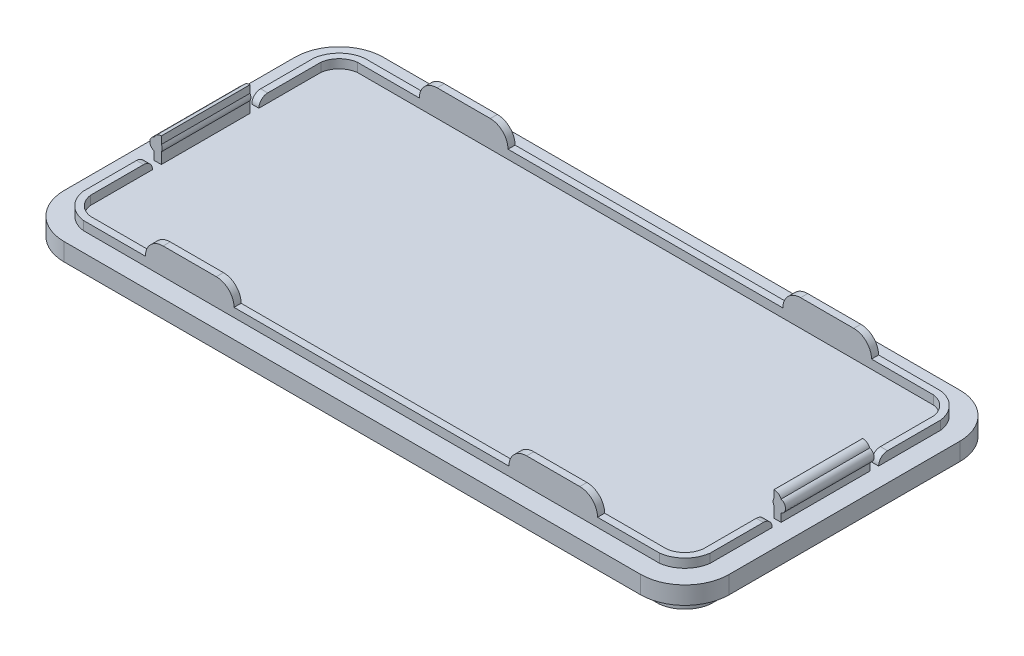
SolidWorks part; units mm, degrees
ref_plane "前视基准面" through (0, 0, 0) normal (0, 0, 1) x (1, 0, 0)
ref_plane "上视基准面" through (0, 0, 0) normal (0, 1, 0) x (1, 0, 0)
ref_plane "右视基准面" through (0, 0, 0) normal (1, 0, 0) x (0, 0, -1)
sketch "zero" plane through (0, 0, 0) normal (0, 1, 0) x (1, 0, 0)
  line L1 (-29.5, 15) -> (29.5, 15)
  line L2 (-32.5, 12) -> (-32.5, -12)
  line L3 (-29.5, -15) -> (29.5, -15)
  line L4 (32.5, 12) -> (32.5, -12)
  line L5 (-32.5, 15) -> (32.5, -15) construction
  line L6 (-32.5, -15) -> (32.5, 15) construction
  line L7 (-25.7, -15) -> (-14.5, -15)
  line L8 (-25.7, -15) -> (-25.7, -9.6569)
  line L9 (-25.7, -9.6569) -> (-14.5, -9.6569)
  line L10 (-14.5, -15) -> (-14.5, -9.6569)
  line L11 (5.2, -15) -> (12.7, -15)
  line L12 (5.2, -15) -> (5.2, -11)
  line L13 (5.2, -11) -> (12.7, -11)
  line L14 (12.7, -15) -> (12.7, -11)
  line L15 (17.8, -15) -> (25.3, -15)
  line L16 (17.8, -15) -> (17.8, -11)
  line L17 (17.8, -11) -> (25.3, -11)
  line L18 (25.3, -15) -> (25.3, -11)
  line L19 (-32.5, 7.7) -> (-19.5, 7.7)
  line L20 (-32.5, 7.7) -> (-32.5, -4.3)
  line L21 (-32.5, -4.3) -> (-19.5, -4.3)
  line L22 (-19.5, 7.7) -> (-19.5, -4.3)
  line L23 (-25.5, 14) -> (25.5, 14)
  line L24 (-25.5, 14) -> (-25.5, 8.8)
  line L25 (-25.5, 8.8) -> (25.5, 8.8)
  line L26 (25.5, 14) -> (25.5, 8.8)
  line L27 (-19.5, 7.2329) -> (-35.5, 7.2329)
  line L28 (-19.5, 7.2329) -> (-19.5, -3.7671)
  line L29 (-19.5, -3.7671) -> (-35.5, -3.7671)
  line L30 (-35.5, 7.2329) -> (-35.5, -3.7671)
  arc A0 (29.5, -15) -> (32.5, -12) centre (29.5, -12) ccw
  arc A1 (29.5, 15) -> (32.5, 12) centre (29.5, 12) cw
  arc A2 (-32.5, -12) -> (-29.5, -15) centre (-29.5, -12) ccw
  arc A3 (-29.5, 15) -> (-32.5, 12) centre (-29.5, 12) ccw
  circle A4 centre (-29, 11.4) radius 3
  circle A5 centre (-29, -11.5) radius 3
  circle A6 centre (29, 11.4) radius 3
  circle A7 centre (29, -11.5) radius 3
  circle A8 centre (-29, 11.4) radius 1.375
  circle A9 centre (-29, -11.5) radius 1.375
  circle A10 centre (29, -11.5) radius 1.375
  circle A11 centre (29, 11.4) radius 1.375
  point P0 (0, 0)
  dimension "D3" = 3
  dimension "D4" = 6
  dimension "D9" = 2.75
  dimension "D1" = 65
  dimension "D2" = 30
  dimension "D5" = 3.6
  dimension "D6" = 3.5
  dimension "D7" = 3.5
  dimension "D8" = 3.5
  dimension "D10" = 12
  dimension "D11" = 7.3
  dimension "D12" = 13
  dimension "D13" = 11.2
  dimension "D14" = 6.8
  dimension "D15" = 19.7
  dimension "D16" = 7.5
  dimension "D17" = 7.5
  dimension "D18" = 5.1
  dimension "D19" = 4
  dimension "D20" = 5.2
  dimension "D21" = 7
  dimension "D22" = 7
  dimension "D23" = 1
  dimension "D24" = 11
  dimension "D25" = 16
sketch "sugar" plane through (0, 0, 0) normal (0, 1, 0) x (1, 0, 0)
  line L1 (-29.5, 15) -> (29.5, 15)
  line L2 (-32.5, 12) -> (-32.5, -12)
  line L3 (-29.5, -15) -> (29.5, -15)
  line L4 (32.5, 12) -> (32.5, -12)
  line L5 (-32.5, 15) -> (32.5, -15) construction
  line L6 (-32.5, -15) -> (32.5, 15) construction
  line L7 (23.5, -11.5) -> (19.5, -11.5)
  line L8 (23.5, -11.5) -> (23.5, -13.9082)
  line L9 (23.5, -13.9082) -> (19.5, -13.9082)
  line L10 (19.5, -11.5) -> (19.5, -13.9082)
  line L11 (16, -11.0071) -> (8.5, -11.0071)
  line L12 (16, -11.0071) -> (16, -15)
  line L13 (16, -15) -> (8.5, -15)
  line L14 (8.5, -11.0071) -> (8.5, -15)
  line L15 (20.5, -13.9082) -> (22.5, -13.9082)
  line L16 (20.5, -13.9082) -> (20.5, -14.8173)
  line L17 (20.5, -14.8173) -> (22.5, -14.8173)
  line L18 (22.5, -13.9082) -> (22.5, -14.8173)
  arc A0 (29.5, 15) -> (32.5, 12) centre (29.5, 12) cw
  arc A1 (29.5, -15) -> (32.5, -12) centre (29.5, -12) ccw
  arc A2 (-32.5, -12) -> (-29.5, -15) centre (-29.5, -12) ccw
  arc A3 (-29.5, 15) -> (-32.5, 12) centre (-29.5, 12) ccw
  circle A4 centre (-29, 11.4) radius 3
  circle A5 centre (-29, 11.4) radius 1.375
  circle A6 centre (-29, -11.5) radius 3
  circle A7 centre (-29, -11.5) radius 1.375
  circle A8 centre (29, 11.4) radius 3
  circle A9 centre (29, 11.4) radius 1.375
  circle A10 centre (29, -11.5) radius 3
  circle A11 centre (29, -11.5) radius 1.375
  dimension "D3" = 3
  dimension "D1" = 65
  dimension "D2" = 30
  dimension "D4" = 9
  dimension "D5" = 4
  dimension "D6" = 3.5
  dimension "D7" = 7.5
  dimension "D8" = 2
  dimension "D9" = 1
sketch "case" plane through (0, 0, 0) normal (0, 1, 0) x (1, 0, 0)
  line L1 (-34.0422, 18) -> (30.9578, 18)
  line L2 (-39.0422, 13) -> (-39.0422, -13)
  line L3 (-34.0422, -18) -> (30.9578, -18)
  line L4 (35.9578, 13) -> (35.9578, -13)
  line L5 (-39.0422, 18) -> (35.9578, -18) construction
  line L6 (-39.0422, -18) -> (35.9578, 18) construction
  arc A0 (-39.0422, -13) -> (-34.0422, -18) centre (-34.0422, -13) ccw
  arc A1 (30.9578, -18) -> (35.9578, -13) centre (30.9578, -13) ccw
  arc A2 (30.9578, 18) -> (35.9578, 13) centre (30.9578, 13) cw
  arc A3 (-34.0422, 18) -> (-39.0422, 13) centre (-34.0422, 13) ccw
  point P0 (-1.5422, 0)
  point P3 (-1.5422, 0)
  dimension "D3" = 5
  dimension "D1" = 75
  dimension "D2" = 36
extrude "凸台-拉伸2" add sketch "case" along normal blind 2
sketch "草图2" plane through (0, 0, 0) normal (0, 1, 0) x (1, 0, 0)
  line L0 (-39.0422, 13) -> (-39.0422, -13) construction
  line L1 (30.9578, 18) -> (-34.0422, 18) construction
  line L4 (-34.0422, -15.05) -> (30.9578, -15.05)
  line L5 (33.0078, -13) -> (33.0078, 13)
  line L6 (30.9578, 15.05) -> (-34.0422, 15.05)
  line L7 (-36.0922, 13) -> (-36.0922, -13)
  line L12 (33.8078, -13) -> (33.8078, 13)
  line L13 (30.9578, 15.85) -> (-34.0422, 15.85)
  line L14 (-36.8922, 13) -> (-36.8922, -13)
  line L15 (-34.0422, -15.85) -> (30.9578, -15.85)
  arc A4 (30.9578, -15.05) -> (33.0078, -13) centre (30.6303, -12.6725) ccw
  arc A5 (33.0078, 13) -> (30.9578, 15.05) centre (30.6303, 12.6725) ccw
  arc A6 (-34.0422, 15.05) -> (-36.0922, 13) centre (-33.7147, 12.6725) ccw
  arc A7 (-36.0922, -13) -> (-34.0422, -15.05) centre (-33.7147, -12.6725) ccw
  arc A12 (30.9578, -15.85) -> (33.8078, -13) centre (30.535, -12.5772) ccw
  arc A13 (33.8078, 13) -> (30.9578, 15.85) centre (30.535, 12.5772) ccw
  arc A14 (-34.0422, 15.85) -> (-36.8922, 13) centre (-33.6194, 12.5772) ccw
  arc A15 (-36.8922, -13) -> (-34.0422, -15.85) centre (-33.6194, -12.5772) ccw
ref_plane "基准面1" through (0, 2, 0) normal (0, 1, 0) x (1, 0, 0)
sketch "草图3" plane through (0, 2, 0) normal (0, 1, 0) x (1, 0, 0)
  line L4 (-34.0422, -15.05) -> (30.9578, -15.05)
  line L5 (33.0078, -13) -> (33.0078, 13)
  line L6 (30.9578, 15.05) -> (-34.0422, 15.05)
  line L7 (-36.0922, 13) -> (-36.0922, -13)
  line L8 (-34.0422, -15.05) -> (30.9578, -15.05)
  line L9 (33.0078, -13) -> (33.0078, 13)
  line L10 (30.9578, 15.05) -> (-34.0422, 15.05)
  line L11 (-36.0922, 13) -> (-36.0922, -13)
  line L12 (-36.8922, 13) -> (-36.8922, -13)
  line L13 (-34.0422, -15.85) -> (30.9578, -15.85)
  line L14 (33.8078, -13) -> (33.8078, 13)
  line L15 (30.9578, 15.85) -> (-34.0422, 15.85)
  line L16 (-36.8922, 13) -> (-36.8922, -13)
  line L17 (-34.0422, -15.85) -> (30.9578, -15.85)
  line L18 (33.8078, -13) -> (33.8078, 13)
  line L19 (30.9578, 15.85) -> (-34.0422, 15.85)
  arc A4 (30.9578, -15.05) -> (33.0078, -13) centre (30.6303, -12.6725) ccw
  arc A5 (33.0078, 13) -> (30.9578, 15.05) centre (30.6303, 12.6725) ccw
  arc A6 (-34.0422, 15.05) -> (-36.0922, 13) centre (-33.7147, 12.6725) ccw
  arc A7 (-36.0922, -13) -> (-34.0422, -15.05) centre (-33.7147, -12.6725) ccw
  arc A8 (30.9578, -15.05) -> (33.0078, -13) centre (30.6303, -12.6725) ccw
  arc A9 (33.0078, 13) -> (30.9578, 15.05) centre (30.6303, 12.6725) ccw
  arc A10 (-34.0422, 15.05) -> (-36.0922, 13) centre (-33.7147, 12.6725) ccw
  arc A11 (-36.0922, -13) -> (-34.0422, -15.05) centre (-33.7147, -12.6725) ccw
  arc A12 (-36.8922, -13) -> (-34.0422, -15.85) centre (-33.6194, -12.5772) ccw
  arc A13 (30.9578, -15.85) -> (33.8078, -13) centre (30.535, -12.5772) ccw
  arc A14 (33.8078, 13) -> (30.9578, 15.85) centre (30.535, 12.5772) ccw
  arc A15 (-34.0422, 15.85) -> (-36.8922, 13) centre (-33.6194, 12.5772) ccw
  arc A16 (-36.8922, -13) -> (-34.0422, -15.85) centre (-33.6194, -12.5772) ccw
  arc A17 (30.9578, -15.85) -> (33.8078, -13) centre (30.535, -12.5772) ccw
  arc A18 (33.8078, 13) -> (30.9578, 15.85) centre (30.535, 12.5772) ccw
  arc A19 (-34.0422, 15.85) -> (-36.8922, 13) centre (-33.6194, 12.5772) ccw
  dimension "D1" = 0
  dimension "D2" = 0
extrude "凸台-拉伸4" add sketch "草图3" along normal blind 1
ref_plane "基准面3" through (33.8078, 0, 0) normal (1, 0, 0) x (0, 0, -1)
sketch "草图7" plane through (0, 2, 0) normal (0, 1, 0) x (1, 0, 0)
  line L0 (-36.8922, 13) -> (-36.8922, -13) construction
  line L1 (-36.8922, 5) -> (-36.0922, 5)
  line L2 (-36.8922, 5) -> (-36.8922, -5)
  line L3 (-36.8922, -5) -> (-36.0922, -5)
  line L4 (-36.0922, 5) -> (-36.0922, -5)
  line L5 (-36.0922, 13) -> (-36.0922, -13) construction
  point P10 (-36.0922, 0)
  dimension "D1" = 5
  dimension "D2" = 10
extrude "凸台-拉伸8" add sketch "草图7" along normal blind 2.8
ref_plane "基准面5" through (0, 0, 5) normal (0, 0, 1) x (1, 0, 0)
sketch "草图8" plane through (0, 0, 5) normal (0, 0, 1) x (1, 0, 0)
  line L0 (-34.0422, 2) -> (-39.0422, 2) construction
  line L1 (-36.8922, 4.8) -> (-36.8922, 3) construction
  circle A0 centre (-36.6922, 3.6) radius 0.7
  dimension "D1" = 1.4
  dimension "D2" = 1.6
  dimension "D3" = 0.2
extrude "凸台-拉伸9" add sketch "草图8" against normal blind 10
fillet "圆角1" radius 0.85 1 edges at (-36.8922, 4.8, 0)
ref_plane "基准面7" through (-36.8922, 0, 0) normal (-1, 0, 0) x (0, 0, 1)
sketch "草图11" plane through (-36.8922, 0, 0) normal (-1, 0, 0) x (0, 0, 1)
  line L0 (-13, 2) -> (13, 2) construction
  line L1 (5, 3) -> (6, 3)
  line L2 (5, 3) -> (5, 2)
  line L3 (5, 2) -> (6, 2)
  line L4 (6, 3) -> (6, 2)
  line L6 (-5, 3) -> (-6, 3)
  line L7 (-5, 3) -> (-5, 2)
  line L8 (-5, 2) -> (-6, 2)
  line L9 (-6, 3) -> (-6, 2)
  dimension "D1" = 1
  dimension "D2" = 1
extrude "切除-拉伸1" cut sketch "草图11" against normal blind 1.2
fillet "圆角2" radius 1 2 edges at (-36.4922, 3, 6) (-36.4922, 3, -6)
ref_plane "基准面8" through (0, 0, 0) normal (0, -1, 0) x (-1, 0, 0)
sketch "草图13" plane through (0, 3, 0) normal (0, 1, 0) x (1, 0, 0)
  line L0 (33.0078, -13) -> (33.0078, 13) construction
  line L1 (33.0078, 5) -> (33.8078, 5)
  line L2 (33.0078, 5) -> (33.0078, -5)
  line L3 (33.0078, -5) -> (33.8078, -5)
  line L4 (33.8078, 5) -> (33.8078, -5)
  line L5 (33.8078, -13) -> (33.8078, 13) construction
  line L7 (35.9578, -13) -> (35.9578, 13) construction
  point P12 (35.9578, 0)
  point P13 (33.8078, 0)
  dimension "D1" = 10
extrude "凸台-拉伸10" add sketch "草图13" along normal blind 1.8
sketch "草图14" plane through (0, 0, 5) normal (0, 0, 1) x (1, 0, 0)
  line L0 (33.8078, 2) -> (30.9578, 2) construction
  line L1 (33.8078, 4.8) -> (33.8078, 3) construction
  circle A0 centre (33.6078, 3.6) radius 0.7
  dimension "D2" = 1.4
  dimension "D1" = 1.6
  dimension "D3" = 0.2
extrude "凸台-拉伸11" add sketch "草图14" against normal blind 10
fillet "圆角3" radius 0.85 1 edges at (33.8078, 4.8, 0)
sketch "草图15" plane through (0, 3, 0) normal (0, 1, 0) x (1, 0, 0)
  line L0 (33.8078, 5) -> (33.8078, 13) construction
  line L1 (33.0078, 5) -> (33.8078, 5)
  line L2 (33.0078, 5) -> (33.0078, 6)
  line L3 (33.0078, 6) -> (33.8078, 6)
  line L4 (33.8078, 5) -> (33.8078, 6)
  line L5 (33.8078, -13) -> (33.8078, -5) construction
  line L6 (33.0078, -5) -> (33.8078, -5)
  line L7 (33.0078, -5) -> (33.0078, -6)
  line L8 (33.0078, -6) -> (33.8078, -6)
  line L9 (33.8078, -5) -> (33.8078, -6)
  dimension "D1" = 1
  dimension "D2" = 1
extrude "切除-拉伸3" cut sketch "草图15" against normal blind 1
fillet "圆角4" radius 1 2 edges at (33.4078, 3, 6) (33.4078, 3, -6)
sketch "草图16" plane through (0, 2, 0) normal (0, 1, 0) x (1, 0, 0)
  line L4 (-34.0422, -15.05) -> (30.9578, -15.05)
  line L5 (33.0078, -13) -> (33.0078, 13)
  line L6 (30.9578, 15.05) -> (-34.0422, 15.05)
  line L7 (-36.0922, 13) -> (-36.0922, -13)
  line L8 (-34.0422, -15.05) -> (30.9578, -15.05)
  line L9 (33.0078, -13) -> (33.0078, 13)
  line L10 (30.9578, 15.05) -> (-34.0422, 15.05)
  line L11 (-36.0922, 13) -> (-36.0922, -13)
  arc A4 (30.9578, -15.05) -> (33.0078, -13) centre (30.6303, -12.6725) ccw
  arc A5 (33.0078, 13) -> (30.9578, 15.05) centre (30.6303, 12.6725) ccw
  arc A6 (-34.0422, 15.05) -> (-36.0922, 13) centre (-33.7147, 12.6725) ccw
  arc A7 (-36.0922, -13) -> (-34.0422, -15.05) centre (-33.7147, -12.6725) ccw
  arc A8 (30.9578, -15.05) -> (33.0078, -13) centre (30.6303, -12.6725) ccw
  arc A9 (33.0078, 13) -> (30.9578, 15.05) centre (30.6303, 12.6725) ccw
  arc A10 (-34.0422, 15.05) -> (-36.0922, 13) centre (-33.7147, 12.6725) ccw
  arc A11 (-36.0922, -13) -> (-34.0422, -15.05) centre (-33.7147, -12.6725) ccw
  dimension "D1" = 0
extrude "凸台-拉伸12" add sketch "草图2" against normal blind 2
sketch "草图18" plane through (0, 0, 0) normal (0, -1, 0) x (1, 0, 0)
  line L2 (-34.0422, 18) -> (30.9578, 18) construction
  line L3 (-39.0422, -13) -> (-39.0422, 13) construction
  circle A0 centre (-37.3172, 15.9) radius 3.225
  circle A1 centre (-37.3172, 15.9) radius 2.225
  circle A2 centre (-29.3672, 15.9) radius 2.225
  circle A3 centre (-29.3672, 15.9) radius 3.225
  circle A4 centre (-21.4172, 15.9) radius 2.225
  circle A5 centre (-21.4172, 15.9) radius 3.225
  circle A6 centre (-13.4672, 15.9) radius 2.225
  circle A7 centre (-13.4672, 15.9) radius 3.225
  circle A8 centre (-5.5172, 15.9) radius 2.225
  circle A9 centre (-5.5172, 15.9) radius 3.225
  circle A10 centre (2.4328, 15.9) radius 2.225
  circle A11 centre (2.4328, 15.9) radius 3.225
  circle A12 centre (10.3828, 15.9) radius 2.225
  circle A13 centre (10.3828, 15.9) radius 3.225
  circle A14 centre (18.3328, 15.9) radius 2.225
  circle A15 centre (18.3328, 15.9) radius 3.225
  circle A16 centre (26.2828, 15.9) radius 2.225
  circle A17 centre (26.2828, 15.9) radius 3.225
  circle A18 centre (34.2328, 15.9) radius 2.225
  circle A19 centre (34.2328, 15.9) radius 3.225
  circle A20 centre (-29.3672, 7.95) radius 2.225
  circle A21 centre (-29.3672, 7.95) radius 3.225
  circle A22 centre (-21.4172, 7.95) radius 2.225
  circle A23 centre (-21.4172, 7.95) radius 3.225
  circle A24 centre (-13.4672, 7.95) radius 2.225
  circle A25 centre (-13.4672, 7.95) radius 3.225
  circle A26 centre (-5.5172, 7.95) radius 2.225
  circle A27 centre (-5.5172, 7.95) radius 3.225
  circle A28 centre (2.4328, 7.95) radius 2.225
  circle A29 centre (2.4328, 7.95) radius 3.225
  circle A30 centre (10.3828, 7.95) radius 2.225
  circle A31 centre (10.3828, 7.95) radius 3.225
  circle A32 centre (18.3328, 7.95) radius 2.225
  circle A33 centre (18.3328, 7.95) radius 3.225
  circle A34 centre (26.2828, 7.95) radius 2.225
  circle A35 centre (26.2828, 7.95) radius 3.225
  circle A36 centre (34.2328, 7.95) radius 2.225
  circle A37 centre (34.2328, 7.95) radius 3.225
  circle A38 centre (-29.3672, 0) radius 2.225
  circle A39 centre (-29.3672, 0) radius 3.225
  circle A40 centre (-21.4172, 0) radius 2.225
  circle A41 centre (-21.4172, 0) radius 3.225
  circle A42 centre (-13.4672, 0) radius 2.225
  circle A43 centre (-13.4672, 0) radius 3.225
  circle A44 centre (-5.5172, 0) radius 2.225
  circle A45 centre (-5.5172, 0) radius 3.225
  circle A46 centre (2.4328, 0) radius 2.225
  circle A47 centre (2.4328, 0) radius 3.225
  circle A48 centre (10.3828, 0) radius 2.225
  circle A49 centre (10.3828, 0) radius 3.225
  circle A50 centre (18.3328, 0) radius 2.225
  circle A51 centre (18.3328, 0) radius 3.225
  circle A52 centre (26.2828, 0) radius 2.225
  circle A53 centre (26.2828, 0) radius 3.225
  circle A54 centre (34.2328, 0) radius 2.225
  circle A55 centre (34.2328, 0) radius 3.225
  circle A56 centre (-29.3672, -7.95) radius 2.225
  circle A57 centre (-29.3672, -7.95) radius 3.225
  circle A58 centre (-21.4172, -7.95) radius 2.225
  circle A59 centre (-21.4172, -7.95) radius 3.225
  circle A60 centre (-13.4672, -7.95) radius 2.225
  circle A61 centre (-13.4672, -7.95) radius 3.225
  circle A62 centre (-5.5172, -7.95) radius 2.225
  circle A63 centre (-5.5172, -7.95) radius 3.225
  circle A64 centre (2.4328, -7.95) radius 2.225
  circle A65 centre (2.4328, -7.95) radius 3.225
  circle A66 centre (10.3828, -7.95) radius 2.225
  circle A67 centre (10.3828, -7.95) radius 3.225
  circle A68 centre (18.3328, -7.95) radius 2.225
  circle A69 centre (18.3328, -7.95) radius 3.225
  circle A70 centre (26.2828, -7.95) radius 2.225
  circle A71 centre (26.2828, -7.95) radius 3.225
  circle A72 centre (34.2328, -7.95) radius 2.225
  circle A73 centre (34.2328, -7.95) radius 3.225
  circle A74 centre (-29.3672, -15.9) radius 2.225
  circle A75 centre (-29.3672, -15.9) radius 3.225
  circle A76 centre (-21.4172, -15.9) radius 2.225
  circle A77 centre (-21.4172, -15.9) radius 3.225
  circle A78 centre (-13.4672, -15.9) radius 2.225
  circle A79 centre (-13.4672, -15.9) radius 3.225
  circle A80 centre (-5.5172, -15.9) radius 2.225
  circle A81 centre (-5.5172, -15.9) radius 3.225
  circle A82 centre (2.4328, -15.9) radius 2.225
  circle A83 centre (2.4328, -15.9) radius 3.225
  circle A84 centre (10.3828, -15.9) radius 2.225
  circle A85 centre (10.3828, -15.9) radius 3.225
  circle A86 centre (18.3328, -15.9) radius 2.225
  circle A87 centre (18.3328, -15.9) radius 3.225
  circle A88 centre (26.2828, -15.9) radius 2.225
  circle A89 centre (26.2828, -15.9) radius 3.225
  circle A90 centre (34.2328, -15.9) radius 2.225
  circle A91 centre (34.2328, -15.9) radius 3.225
  circle A92 centre (-37.3172, 7.95) radius 2.225
  circle A93 centre (-37.3172, 7.95) radius 3.225
  circle A94 centre (-37.3172, 0) radius 2.225
  circle A95 centre (-37.3172, 0) radius 3.225
  circle A96 centre (-37.3172, -7.95) radius 2.225
  circle A97 centre (-37.3172, -7.95) radius 3.225
  circle A98 centre (-37.3172, -15.9) radius 2.225
  circle A99 centre (-37.3172, -15.9) radius 3.225
  dimension "D1" = 6.45
  dimension "D2" = 4.45
  dimension "D3" = 2.1
  dimension "D4" = 1.725
  dimension "D5" = 10
  dimension "D6" = 5
extrude "凸台-拉伸13" add sketch "草图18" along normal blind 2
sketch "草图20" plane through (0, 0, 0) normal (0, -1, 0) x (1, 0, 0)
  line L4 (30.9578, 15.85) -> (29.5074, 15.85)
  line L5 (-36.8922, -11.1469) -> (-36.8922, -12.7031)
  line L6 (-34.0422, -15.85) -> (-32.5918, -15.85)
  line L7 (-36.8922, -11.1469) -> (-36.8922, -12.7031)
  line L8 (30.9578, 15.85) -> (29.5074, 15.85)
  line L10 (-34.0422, -15.85) -> (-32.5918, -15.85)
  line L12 (-36.0922, 13) -> (-36.0922, -13)
  line L13 (-34.0422, -15.05) -> (30.9578, -15.05)
  line L14 (33.0078, -13) -> (33.0078, 13)
  line L15 (30.9578, 15.05) -> (-34.0422, 15.05)
  line L16 (-36.0922, 13) -> (-36.0922, -13)
  line L17 (-34.0422, -15.05) -> (30.9578, -15.05)
  line L18 (33.0078, -13) -> (33.0078, 13)
  line L19 (30.9578, 15.05) -> (-34.0422, 15.05)
  line L34 (-26.1426, -15.85) -> (-24.6418, -15.85)
  line L35 (-26.1426, -15.85) -> (-24.6418, -15.85)
  line L36 (-18.1926, -15.85) -> (-16.6918, -15.85)
  line L37 (-18.1926, -15.85) -> (-16.6918, -15.85)
  line L38 (-10.2426, -15.85) -> (-8.7418, -15.85)
  line L39 (-10.2426, -15.85) -> (-8.7418, -15.85)
  line L40 (-2.2926, -15.85) -> (-0.7918, -15.85)
  line L41 (-2.2926, -15.85) -> (-0.7918, -15.85)
  line L42 (5.6574, -15.85) -> (7.1582, -15.85)
  line L43 (5.6574, -15.85) -> (7.1582, -15.85)
  line L44 (13.6074, -15.85) -> (15.1082, -15.85)
  line L45 (13.6074, -15.85) -> (15.1082, -15.85)
  line L46 (21.5574, -15.85) -> (23.0582, -15.85)
  line L47 (21.5574, -15.85) -> (23.0582, -15.85)
  line L48 (29.5074, -15.85) -> (30.9578, -15.85)
  line L49 (29.5074, -15.85) -> (30.9578, -15.85)
  line L50 (33.8078, -12.7031) -> (33.8078, -11.1469)
  line L51 (33.8078, -12.7031) -> (33.8078, -11.1469)
  line L52 (33.8078, -4.7531) -> (33.8078, -3.1969)
  line L53 (33.8078, -4.7531) -> (33.8078, -3.1969)
  line L54 (33.8078, 3.1969) -> (33.8078, 4.7531)
  line L55 (33.8078, 3.1969) -> (33.8078, 4.7531)
  line L56 (33.8078, 11.1469) -> (33.8078, 12.7031)
  line L57 (33.8078, 11.1469) -> (33.8078, 12.7031)
  line L58 (23.0582, 15.85) -> (21.5574, 15.85)
  line L59 (23.0582, 15.85) -> (21.5574, 15.85)
  line L60 (15.1082, 15.85) -> (13.6074, 15.85)
  line L61 (15.1082, 15.85) -> (13.6074, 15.85)
  line L62 (7.1582, 15.85) -> (5.6574, 15.85)
  line L63 (7.1582, 15.85) -> (5.6574, 15.85)
  line L64 (-0.7918, 15.85) -> (-2.2926, 15.85)
  line L65 (-0.7918, 15.85) -> (-2.2926, 15.85)
  line L66 (-8.7418, 15.85) -> (-10.2426, 15.85)
  line L67 (-8.7418, 15.85) -> (-10.2426, 15.85)
  line L68 (-16.6918, 15.85) -> (-18.1926, 15.85)
  line L69 (-16.6918, 15.85) -> (-18.1926, 15.85)
  line L70 (-24.6418, 15.85) -> (-26.1426, 15.85)
  line L71 (-24.6418, 15.85) -> (-26.1426, 15.85)
  line L72 (-32.5918, 15.85) -> (-34.0422, 15.85)
  line L73 (-32.5918, 15.85) -> (-34.0422, 15.85)
  line L74 (-36.8922, 12.7031) -> (-36.8922, 11.1469)
  line L75 (-36.8922, 12.7031) -> (-36.8922, 11.1469)
  line L76 (-36.8922, 4.7531) -> (-36.8922, 3.1969)
  line L77 (-36.8922, 4.7531) -> (-36.8922, 3.1969)
  line L78 (-36.8922, -3.1969) -> (-36.8922, -4.7531)
  line L79 (-36.8922, -3.1969) -> (-36.8922, -4.7531)
  arc A4 (31.0083, 15.8431) -> (30.9578, 15.85) centre (30.535, 12.5772) ccw
  arc A5 (-34.0422, 15.85) -> (-34.0927, 15.8431) centre (-33.6194, 12.5772) ccw
  arc A6 (-34.0927, -15.8431) -> (-34.0422, -15.85) centre (-33.6194, -12.5772) ccw
  arc A7 (30.9578, -15.85) -> (31.0083, -15.8431) centre (30.535, -12.5772) ccw
  arc A8 (31.0083, 15.8431) -> (30.9578, 15.85) centre (30.535, 12.5772) ccw
  arc A9 (-34.0422, 15.85) -> (-34.0927, 15.8431) centre (-33.6194, 12.5772) ccw
  arc A10 (-34.0927, -15.8431) -> (-34.0422, -15.85) centre (-33.6194, -12.5772) ccw
  arc A11 (30.9578, -15.85) -> (31.0083, -15.8431) centre (30.535, -12.5772) ccw
  arc A12 (-36.0922, -13) -> (-34.0422, -15.05) centre (-33.7147, -12.6725) ccw
  arc A13 (30.9578, -15.05) -> (33.0078, -13) centre (30.6303, -12.6725) ccw
  arc A14 (33.0078, 13) -> (30.9578, 15.05) centre (30.6303, 12.6725) ccw
  arc A15 (-34.0422, 15.05) -> (-36.0922, 13) centre (-33.7147, 12.6725) ccw
  arc A16 (-36.0922, -13) -> (-34.0422, -15.05) centre (-33.7147, -12.6725) ccw
  arc A17 (30.9578, -15.05) -> (33.0078, -13) centre (30.6303, -12.6725) ccw
  arc A18 (33.0078, 13) -> (30.9578, 15.05) centre (30.6303, 12.6725) ccw
  arc A19 (-34.0422, 15.05) -> (-36.0922, 13) centre (-33.7147, 12.6725) ccw
  arc A38 (-36.8922, -12.7031) -> (-34.0927, -15.8431) centre (-37.3172, -15.9) ccw
  arc A39 (-36.8922, -12.7031) -> (-34.0927, -15.8431) centre (-37.3172, -15.9) ccw
  arc A40 (-32.5918, -15.85) -> (-26.1426, -15.85) centre (-29.3672, -15.9) ccw
  arc A41 (-32.5918, -15.85) -> (-26.1426, -15.85) centre (-29.3672, -15.9) ccw
  arc A42 (-24.6418, -15.85) -> (-18.1926, -15.85) centre (-21.4172, -15.9) ccw
  arc A43 (-24.6418, -15.85) -> (-18.1926, -15.85) centre (-21.4172, -15.9) ccw
  arc A44 (-16.6918, -15.85) -> (-10.2426, -15.85) centre (-13.4672, -15.9) ccw
  arc A45 (-16.6918, -15.85) -> (-10.2426, -15.85) centre (-13.4672, -15.9) ccw
  arc A46 (-8.7418, -15.85) -> (-2.2926, -15.85) centre (-5.5172, -15.9) ccw
  arc A47 (-8.7418, -15.85) -> (-2.2926, -15.85) centre (-5.5172, -15.9) ccw
  arc A48 (-0.7918, -15.85) -> (5.6574, -15.85) centre (2.4328, -15.9) ccw
  arc A49 (-0.7918, -15.85) -> (5.6574, -15.85) centre (2.4328, -15.9) ccw
  arc A50 (7.1582, -15.85) -> (13.6074, -15.85) centre (10.3828, -15.9) ccw
  arc A51 (7.1582, -15.85) -> (13.6074, -15.85) centre (10.3828, -15.9) ccw
  arc A52 (15.1082, -15.85) -> (21.5574, -15.85) centre (18.3328, -15.9) ccw
  arc A53 (15.1082, -15.85) -> (21.5574, -15.85) centre (18.3328, -15.9) ccw
  arc A54 (23.0582, -15.85) -> (29.5074, -15.85) centre (26.2828, -15.9) ccw
  arc A55 (23.0582, -15.85) -> (29.5074, -15.85) centre (26.2828, -15.9) ccw
  arc A56 (31.0083, -15.8431) -> (33.8078, -12.7031) centre (34.2328, -15.9) ccw
  arc A57 (31.0083, -15.8431) -> (33.8078, -12.7031) centre (34.2328, -15.9) ccw
  arc A58 (33.8078, -11.1469) -> (33.8078, -4.7531) centre (34.2328, -7.95) ccw
  arc A59 (33.8078, -11.1469) -> (33.8078, -4.7531) centre (34.2328, -7.95) ccw
  arc A60 (33.8078, -3.1969) -> (33.8078, 3.1969) centre (34.2328, 0) ccw
  arc A61 (33.8078, -3.1969) -> (33.8078, 3.1969) centre (34.2328, 0) ccw
  arc A62 (33.8078, 4.7531) -> (33.8078, 11.1469) centre (34.2328, 7.95) ccw
  arc A63 (33.8078, 4.7531) -> (33.8078, 11.1469) centre (34.2328, 7.95) ccw
  arc A64 (33.8078, 12.7031) -> (31.0083, 15.8431) centre (34.2328, 15.9) ccw
  arc A65 (33.8078, 12.7031) -> (31.0083, 15.8431) centre (34.2328, 15.9) ccw
  arc A66 (29.5074, 15.85) -> (23.0582, 15.85) centre (26.2828, 15.9) ccw
  arc A67 (29.5074, 15.85) -> (23.0582, 15.85) centre (26.2828, 15.9) ccw
  arc A68 (21.5574, 15.85) -> (15.1082, 15.85) centre (18.3328, 15.9) ccw
  arc A69 (21.5574, 15.85) -> (15.1082, 15.85) centre (18.3328, 15.9) ccw
  arc A70 (13.6074, 15.85) -> (7.1582, 15.85) centre (10.3828, 15.9) ccw
  arc A71 (13.6074, 15.85) -> (7.1582, 15.85) centre (10.3828, 15.9) ccw
  arc A72 (5.6574, 15.85) -> (-0.7918, 15.85) centre (2.4328, 15.9) ccw
  arc A73 (5.6574, 15.85) -> (-0.7918, 15.85) centre (2.4328, 15.9) ccw
  arc A74 (-2.2926, 15.85) -> (-8.7418, 15.85) centre (-5.5172, 15.9) ccw
  arc A75 (-2.2926, 15.85) -> (-8.7418, 15.85) centre (-5.5172, 15.9) ccw
  arc A76 (-10.2426, 15.85) -> (-16.6918, 15.85) centre (-13.4672, 15.9) ccw
  arc A77 (-10.2426, 15.85) -> (-16.6918, 15.85) centre (-13.4672, 15.9) ccw
  arc A78 (-18.1926, 15.85) -> (-24.6418, 15.85) centre (-21.4172, 15.9) ccw
  arc A79 (-18.1926, 15.85) -> (-24.6418, 15.85) centre (-21.4172, 15.9) ccw
  arc A80 (-26.1426, 15.85) -> (-32.5918, 15.85) centre (-29.3672, 15.9) ccw
  arc A81 (-26.1426, 15.85) -> (-32.5918, 15.85) centre (-29.3672, 15.9) ccw
  arc A82 (-34.0927, 15.8431) -> (-36.8922, 12.7031) centre (-37.3172, 15.9) ccw
  arc A83 (-34.0927, 15.8431) -> (-36.8922, 12.7031) centre (-37.3172, 15.9) ccw
  arc A84 (-36.8922, 11.1469) -> (-36.8922, 4.7531) centre (-37.3172, 7.95) ccw
  arc A85 (-36.8922, 11.1469) -> (-36.8922, 4.7531) centre (-37.3172, 7.95) ccw
  arc A86 (-36.8922, 3.1969) -> (-36.8922, -3.1969) centre (-37.3172, 0) ccw
  arc A87 (-36.8922, 3.1969) -> (-36.8922, -3.1969) centre (-37.3172, 0) ccw
  arc A88 (-36.8922, -4.7531) -> (-36.8922, -11.1469) centre (-37.3172, -7.95) ccw
  arc A89 (-36.8922, -4.7531) -> (-36.8922, -11.1469) centre (-37.3172, -7.95) ccw
  dimension "D1" = 0
  dimension "D2" = 0
extrude "切除-拉伸4" cut sketch "草图20" along normal blind 2
sketch "草图21" plane through (0, 0, 0) normal (0, -1, 0) x (1, 0, 0)
  line L4 (30.9578, 15.05) -> (-34.0422, 15.05)
  line L5 (33.0078, -13) -> (33.0078, 13)
  line L6 (-34.0422, -15.05) -> (30.9578, -15.05)
  line L7 (-36.0922, 13) -> (-36.0922, -13)
  line L8 (30.9578, 15.05) -> (-34.0422, 15.05)
  line L9 (33.0078, -13) -> (33.0078, 13)
  line L10 (-34.0422, -15.05) -> (30.9578, -15.05)
  line L11 (-36.0922, 13) -> (-36.0922, -13)
  line L12 (-36.8922, 13) -> (-36.8922, -13)
  line L13 (30.9578, 15.85) -> (-34.0422, 15.85)
  line L14 (33.8078, -13) -> (33.8078, 13)
  line L15 (-34.0422, -15.85) -> (30.9578, -15.85)
  line L16 (-36.8922, 13) -> (-36.8922, -13)
  line L17 (30.9578, 15.85) -> (-34.0422, 15.85)
  line L18 (33.8078, -13) -> (33.8078, 13)
  line L19 (-34.0422, -15.85) -> (30.9578, -15.85)
  arc A4 (33.0078, 13) -> (30.9578, 15.05) centre (30.6303, 12.6725) ccw
  arc A5 (30.9578, -15.05) -> (33.0078, -13) centre (30.6303, -12.6725) ccw
  arc A6 (-36.0922, -13) -> (-34.0422, -15.05) centre (-33.7147, -12.6725) ccw
  arc A7 (-34.0422, 15.05) -> (-36.0922, 13) centre (-33.7147, 12.6725) ccw
  arc A8 (33.0078, 13) -> (30.9578, 15.05) centre (30.6303, 12.6725) ccw
  arc A9 (30.9578, -15.05) -> (33.0078, -13) centre (30.6303, -12.6725) ccw
  arc A10 (-36.0922, -13) -> (-34.0422, -15.05) centre (-33.7147, -12.6725) ccw
  arc A11 (-34.0422, 15.05) -> (-36.0922, 13) centre (-33.7147, 12.6725) ccw
  arc A12 (-34.0422, 15.85) -> (-36.8922, 13) centre (-33.6194, 12.5772) ccw
  arc A13 (33.8078, 13) -> (30.9578, 15.85) centre (30.535, 12.5772) ccw
  arc A14 (30.9578, -15.85) -> (33.8078, -13) centre (30.535, -12.5772) ccw
  arc A15 (-36.8922, -13) -> (-34.0422, -15.85) centre (-33.6194, -12.5772) ccw
  arc A16 (-34.0422, 15.85) -> (-36.8922, 13) centre (-33.6194, 12.5772) ccw
  arc A17 (33.8078, 13) -> (30.9578, 15.85) centre (30.535, 12.5772) ccw
  arc A18 (30.9578, -15.85) -> (33.8078, -13) centre (30.535, -12.5772) ccw
  arc A19 (-36.8922, -13) -> (-34.0422, -15.85) centre (-33.6194, -12.5772) ccw
  dimension "D1" = 0
  dimension "D2" = 0
extrude "凸台-拉伸14" add sketch "草图21" along normal blind 2
sketch "草图22" plane through (0, 3, 0) normal (0, 1, 0) x (1, 0, 0)
  line L0 (30.9578, 15.85) -> (-34.0422, 15.85) construction
  line L1 (-27.0422, 15.85) -> (-17.0422, 15.85)
  line L2 (-27.0422, 15.85) -> (-27.0422, 15.05)
  line L3 (-27.0422, 15.05) -> (-17.0422, 15.05)
  line L4 (-17.0422, 15.85) -> (-17.0422, 15.05)
  line L5 (30.9578, 15.05) -> (-34.0422, 15.05) construction
  line L6 (-34.0422, -15.05) -> (30.9578, -15.05) construction
  line L7 (13.9578, 15.85) -> (23.9578, 15.85)
  line L8 (13.9578, 15.85) -> (13.9578, 15.05)
  line L9 (13.9578, 15.05) -> (23.9578, 15.05)
  line L10 (23.9578, 15.85) -> (23.9578, 15.05)
  line L11 (-27.0422, -15.05) -> (-17.0422, -15.05)
  line L12 (-27.0422, -15.05) -> (-27.0422, -15.85)
  line L13 (-27.0422, -15.85) -> (-17.0422, -15.85)
  line L14 (-17.0422, -15.05) -> (-17.0422, -15.85)
  line L15 (-34.0422, -15.85) -> (30.9578, -15.85) construction
  line L16 (35.9578, -13) -> (35.9578, 13) construction
  line L17 (13.9578, -15.05) -> (23.9578, -15.05)
  line L18 (13.9578, -15.05) -> (13.9578, -15.85)
  line L19 (13.9578, -15.85) -> (23.9578, -15.85)
  line L20 (23.9578, -15.05) -> (23.9578, -15.85)
  line L21 (-39.0422, 13) -> (-39.0422, -13) construction
  dimension "D1" = 10
  dimension "D2" = 10
  dimension "D3" = 10
  dimension "D4" = 10
  dimension "D5" = 12
  dimension "D6" = 12
  dimension "D7" = 12
  dimension "D8" = 12
extrude "凸台-拉伸16" add sketch "草图22" along normal blind 2
fillet "圆角5" radius 2 8 edges at (-27.0422, 5, 15.45) (-17.0422, 5, 15.45) (23.9578, 5, 15.45) (13.9578, 5, 15.45) (23.9578, 5, -15.45) (13.9578, 5, -15.45) (-17.0422, 5, -15.45) (-27.0422, 5, -15.45)
